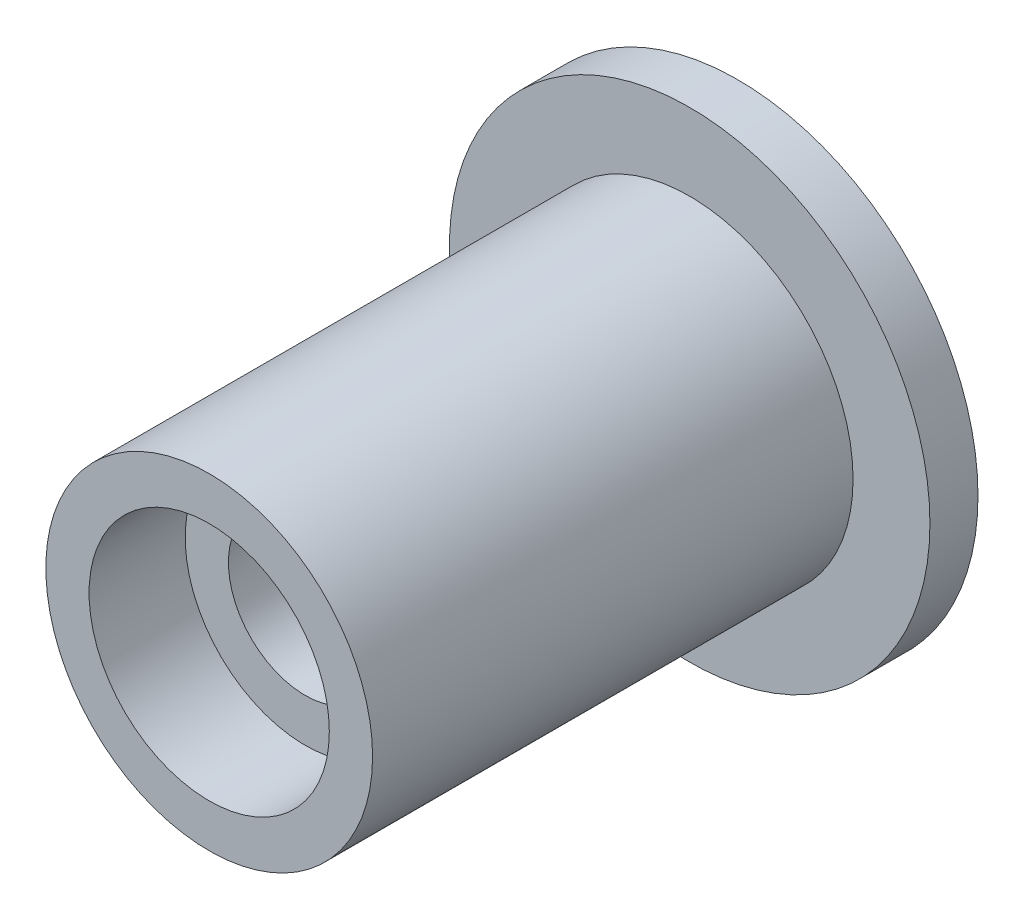
SolidWorks part; units mm, degrees
ref_plane "Front Plane" through (0, 0, 0) normal (0, 0, 1) x (1, 0, 0)
ref_plane "Top Plane" through (0, 0, 0) normal (0, 1, 0) x (1, 0, 0)
ref_plane "Right Plane" through (0, 0, 0) normal (1, 0, 0) x (0, 0, -1)
ref_axis "X" through (-88.99, 0, 0) along (1, 0, 0)
ref_axis "Y" through (0, 55, 0) along (0, -1, 0)
ref_axis "Z" through (0, 0, -88.99) along (0, 0, 1)
sketch "Sketch1" plane through (0, 0, 0) normal (0, 0, 1) x (1, 0, 0)
  circle A0 centre (0, 0) radius 3.4
  circle A1 centre (0, 0) radius 1.6
  circle A2 centre (0, 0) radius 2.5
  circle A3 centre (0, 0) radius 5
  dimension "D1" = 6.8
  dimension "D2" = 3.2
  dimension "D3" = 5
  dimension "D4" = 10
extrude "Boss-Extrude1" add sketch "Sketch1" against normal blind 1 contours A3 | A1
extrude "Boss-Extrude2" add sketch "Sketch1<3>" along normal blind 10 contours A0 A2 region at (-3.3038, 0, 0)
sketch "Sketch1<3>" plane through (0, 0, 0) normal (0, 0, 1) x (1, 0, 0) same geometry as "Sketch1"
extrude "Boss-Extrude3" add sketch "Sketch1<4>" along normal blind 8 contours A2 A1 region at (-2.4293, 0, 0)
sketch "Sketch1<4>" plane through (0, 0, 0) normal (0, 0, 1) x (1, 0, 0) same geometry as "Sketch1"
